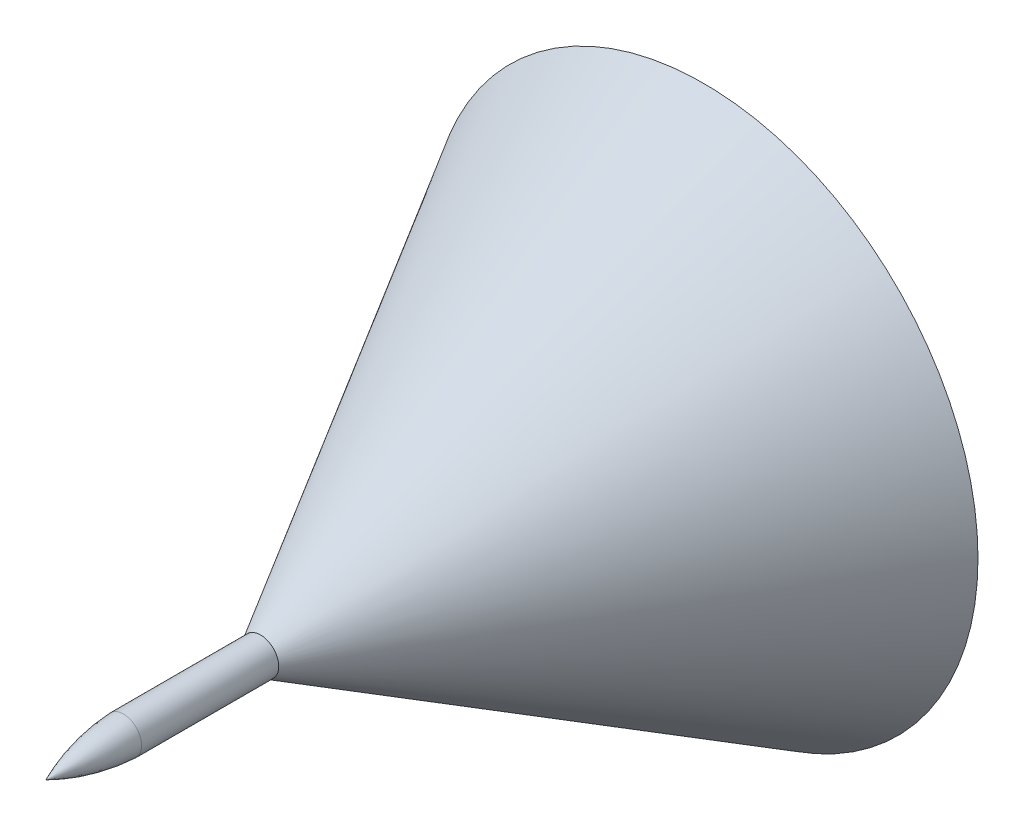
SolidWorks part; units mm, degrees
ref_plane "前基準面" through (0, 0, 0) normal (0, 0, 1) x (1, 0, 0)
ref_plane "上基準面" through (0, 0, 0) normal (0, 1, 0) x (1, 0, 0)
ref_plane "右基準面" through (0, 0, 0) normal (1, 0, 0) x (0, 0, -1)
sketch "草圖1" plane through (0, 0, 0) normal (1, 0, 0) x (0, 0, -1)
  line L0 (0, 0) -> (25.9808, 15)
  line L1 (0, 0) -> (2, 0)
  line L2 (0, 0) -> (75.9875, 0) construction
  line L3 (2, 0) -> (25.9808, 13.8453)
  line L4 (25.9808, 15) -> (25.9808, 13.8453)
  dimension "D1" = 30
  dimension "D3" = 15
  dimension "D5" = 1
revolve "旋轉1" add sketch "草圖1" angle 360 about L2
sketch "草圖4" plane through (0, 0, -25.9808) normal (0, 0, -1) x (-1, 0, 0)
  line L0 (0, 15) -> (0, -15) construction
  line L1 (-15, 0) -> (15, 0) construction
  circle A0 centre (0, 0) radius 15 construction
ref_plane "平面2" through (0, 0, 0) normal (0, 1, 0) x (1, 0, 0)
sketch "草圖5" plane through (0, 0, 0) normal (0, 1, 0) x (1, 0, 0)
  line L0 (-1, -5.7679) -> (-1, 1.7321)
  line L1 (-15, 25.9808) -> (0, 0) construction
  line L2 (0, 0) -> (0, -10)
  line L3 (-1, 1.7321) -> (0, 0)
  spline S0 degree 2 poles (-1, -5.7679) (-0.9025, -7.9799) (0, -10) knots 0 0 0 1 1 1
  point P8 (-1, -7.5125)
  point P9 (0, 0)
  point P10 (-0.6905, -7.9771)
  dimension "D1" = 10
  dimension "D2" = 1
  dimension "D3" = 7.5
revolve "旋轉2" add sketch "草圖5" angle 360 about L2
